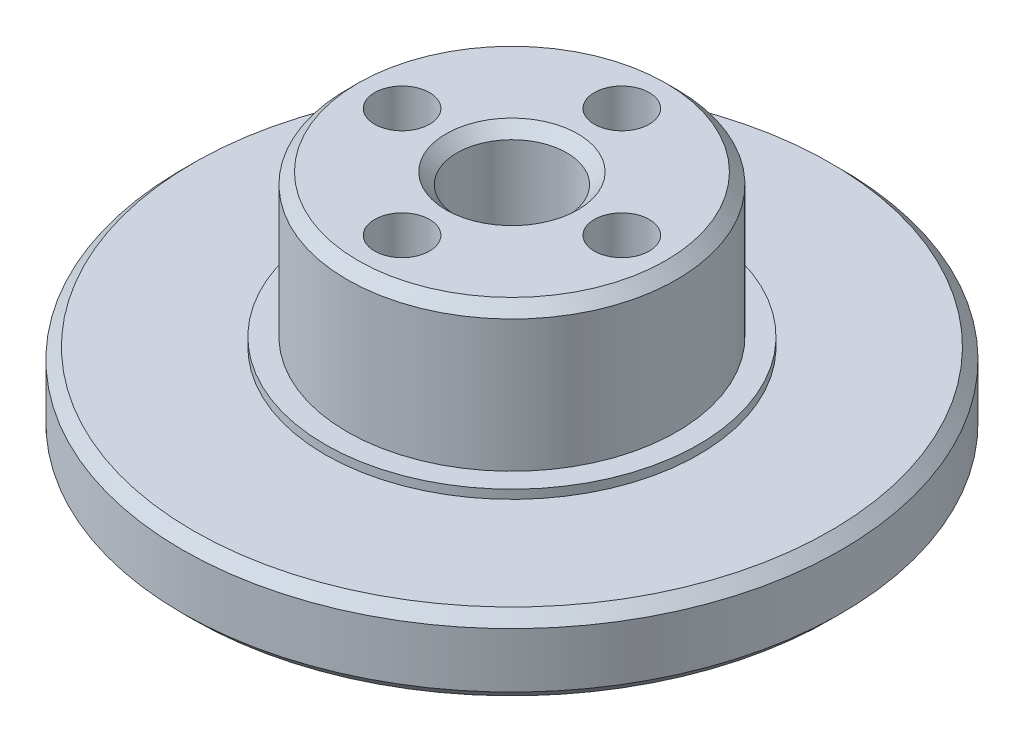
SolidWorks part; units mm, degrees
ref_plane "前视基准面" through (0, 0, 0) normal (0, 0, 1) x (1, 0, 0)
ref_plane "上视基准面" through (0, 0, 0) normal (0, 1, 0) x (1, 0, 0)
ref_plane "右视基准面" through (0, 0, 0) normal (1, 0, 0) x (0, 0, -1)
other "Configuration Table"
sketch "草图1" plane through (0, 0, 0) normal (0, 1, 0) x (1, 0, 0)
  circle A0 centre (0, 0) radius 11.525 construction
  circle A1 centre (0, 11.525) radius 2
  circle A2 centre (9.9809, 5.7625) radius 2
  circle A3 centre (9.9809, -5.7625) radius 2
  circle A4 centre (0, -11.525) radius 2
  circle A5 centre (-9.9809, -5.7625) radius 2
  circle A6 centre (-9.9809, 5.7625) radius 2
  circle A8 centre (0, 0) radius 15
  point P18 (0, 0)
  dimension "D1" = 23.05
  dimension "D2" = 4
  dimension "D5" = 30
  dimension "D3" = 6
extrude "凸台-拉伸1" add sketch "草图1" along normal blind 2
sketch "草图2" plane through (0, 2, 0) normal (0, 1, 0) x (1, 0, 0)
  circle A0 centre (0, 0) radius 15
extrude "凸台-拉伸2" add sketch "草图2" along normal blind 1.5
sketch "草图3" plane through (0, 3.5, 0) normal (0, 1, 0) x (1, 0, 0)
  circle A0 centre (0, 0) radius 8.5
  dimension "D1" = 17
extrude "凸台-拉伸3" add sketch "草图3" along normal blind 0.4
sketch "草图4" plane through (0, 3.9, 0) normal (0, 1, 0) x (1, 0, 0)
  circle A0 centre (0, 0) radius 7.5
  dimension "D1" = 15
extrude "凸台-拉伸4" add sketch "草图4" along normal blind 6.5
sketch "草图5" plane through (0, 10.4, 0) normal (0, 1, 0) x (1, 0, 0)
  circle A0 centre (0, 5) radius 1.25
  circle A1 centre (5, 0) radius 1.25
  circle A2 centre (0, -5) radius 1.25
  circle A3 centre (-5, 0) radius 1.25
  circle A4 centre (0, 0) radius 2.5
  point P12 (0, 0)
  dimension "D1" = 2.5
  dimension "D2" = 5
  dimension "D4" = 5
  dimension "D3" = 4
extrude "切除-拉伸1" cut sketch "草图5" against normal blind 5
chamfer "倒角1" distance 0.5 angle 45 10 edges at (-9.9809, 0, -3.7625) (-9.9809, 0, 7.7625) (0, 0, 13.525) (9.9809, 0, 7.7625) (9.9809, 0, -3.7625) (0, 0, -9.525) (0, 0, 15) (0, 10.4, 7.5) (0, 3.5, 15) (0, 10.4, 2.5)
sketch "草图7" plane through (0, 5.4, 0) normal (0, 1, 0) x (1, 0, 0)
  circle A2 centre (0, 0) radius 2.5 construction
  circle A3 centre (0, 0) radius 2.5
extrude "切除-拉伸4" cut sketch "草图7" against normal through all
sketch "草图8" plane through (0, 0, 0) normal (0, -1, 0) x (-1, 0, 0)
  circle A0 centre (0, 0) radius 6
  dimension "D1" = 6
extrude "切除-拉伸5" cut sketch "草图8" against normal blind 2
chamfer "倒角2" distance 0.5 angle 45 3 edges at (0, 0, -6) (0, 2, -2.5) (0, 2, -6)
